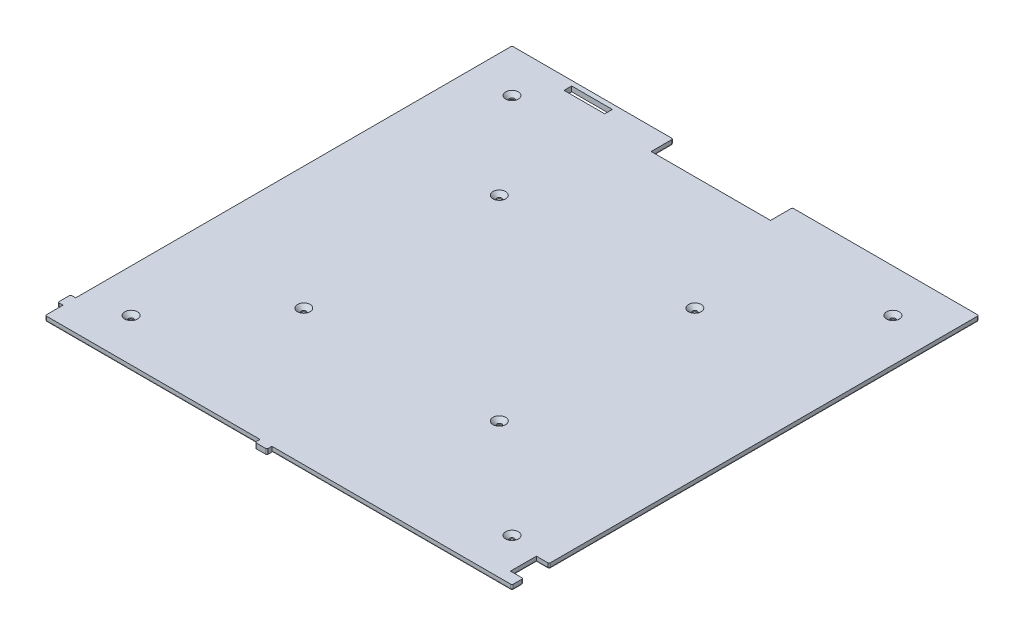
SolidWorks part; units mm, degrees
ref_plane "Front Plane" through (0, 0, 0) normal (0, 0, 1) x (1, 0, 0)
ref_plane "Top Plane" through (0, 0, 0) normal (0, 1, 0) x (1, 0, 0)
ref_plane "Right Plane" through (0, 0, 0) normal (1, 0, 0) x (0, 0, -1)
sketch "Sketch1" plane through (0, 0, 0) normal (0, 1, 0) x (1, 0, 0)
  line L0 (-92, 85.9) -> (-92, -85.9) construction
  line L1 (-28.4, 85.9) -> (-92, 85.9) construction
  line L2 (-28.4, 77.3) -> (-28.4, 85.9) construction
  line L3 (18.4, 77.3) -> (-28.4, 77.3) construction
  line L4 (18.4, 85.9) -> (18.4, 77.3) construction
  line L5 (92, 85.9) -> (18.4, 85.9) construction
  line L6 (92, -83.5) -> (92, 85.9) construction
  line L7 (87, -83.5) -> (92, -83.5) construction
  line L8 (87, -93.5) -> (87, -83.5) construction
  line L9 (92, -93.5) -> (87, -93.5) construction
  line L10 (92, -98.1) -> (92, -93.5) construction
  line L11 (-92, -98.1) -> (92, -98.1) construction
  line L12 (-92, -91.1) -> (-92, -98.1) construction
  line L13 (-94, -91.1) -> (-92, -91.1) construction
  line L14 (-94, -85.9) -> (-94, -91.1) construction
  line L15 (-92, -85.9) -> (-94, -85.9) construction
  line L16 (-91.9, 85.8) -> (-91.9, -86)
  line L17 (-91.9, -86) -> (-93.9, -86)
  line L18 (-93.9, -86) -> (-93.9, -91)
  line L19 (-93.9, -91) -> (-91.9, -91)
  line L20 (-91.9, -91) -> (-91.9, -98)
  line L21 (-91.9, -98) -> (91.9, -98)
  line L22 (91.9, -98) -> (91.9, -93.6)
  line L23 (91.9, -93.6) -> (86.9, -93.6)
  line L24 (86.9, -93.6) -> (86.9, -83.4)
  line L25 (86.9, -83.4) -> (91.9, -83.4)
  line L26 (91.9, -83.4) -> (91.9, 85.8)
  line L27 (91.9, 85.8) -> (18.5, 85.8)
  line L28 (18.5, 85.8) -> (18.5, 77.2)
  line L29 (18.5, 77.2) -> (-28.5, 77.2)
  line L30 (-28.5, 77.2) -> (-28.5, 85.8)
  line L31 (-28.5, 85.8) -> (-91.9, 85.8)
  point P16 (0, -98.1)
  point P18 (-92, 0)
  dimension "D1" = 169.4
  dimension "D2" = 171.8
  dimension "D3" = 63.6
  dimension "D4" = 73.6
  dimension "D5" = 46.8
  dimension "D6" = 8.6
  dimension "D7" = 10
  dimension "D8" = 5
  dimension "D9" = 5.2
  dimension "D10" = 7
  dimension "D11" = 2
  dimension "D12" = 0.1
extrude "Boss-Extrude1" add sketch "Sketch1" along normal blind 2
sketch "Sketch2" plane through (0, 0, 0) normal (0, -1, 0) x (1, 0, 0)
  circle A0 centre (75, -68.9) radius 1
  circle A1 centre (-75, -68.9) radius 1
  circle A2 centre (-75, 81.1) radius 1
  circle A3 centre (75, 81.1) radius 1
  circle A4 centre (33.5, -32.4) radius 1
  circle A5 centre (-43.5, -32.4) radius 1
  circle A6 centre (-43.5, 44.6) radius 1
  circle A7 centre (33.5, 44.6) radius 1
  dimension "D1" = 2
  dimension "D2" = 2
  dimension "D3" = 2
  dimension "D4" = 2
  dimension "D5" = 2
  dimension "D6" = 2
  dimension "D7" = 2
  dimension "D8" = 2
extrude "Cut-Extrude1" cut sketch "Sketch2" against normal through all
chamfer "Chamfer1" distance 1.5 distance2 1.5 1 edges at (-75, 2, -69.9)
chamfer "Chamfer2" distance 1.5 angle 45 7 edges at (75, 2, 80.1) (33.5, 2, 43.6) (75, 2, -69.9) (33.5, 2, -33.4) (-43.5, 2, -33.4) (-43.5, 2, 43.6) (-75, 2, 80.1)
fillet "Fillet1" radius 0.5 16 edges at (-91.9, 0, 0.1) (-92.9, 0, 86) (-93.9, 0, 88.5) (-92.9, 0, 91) (-91.9, 0, 94.5) (0, 0, 98) (91.9, 0, 95.8) (89.4, 0, 93.6) (86.9, 0, 88.5) (89.4, 0, 83.4) (91.9, 0, -1.2) (55.2, 0, -85.8) (18.5, 0, -81.5) (-5, 0, -77.2) (-28.5, 0, -81.5) (-60.2, 0, -85.8)
fillet "Fillet2" radius 0.5 20 edges at (-91.7536, 0.1464, -85.6536) (-28.6464, 0.1464, -85.6536) (18.6464, 0.1464, -85.6536) (91.7536, 0.1464, -85.6536) (91.7536, 0.1464, 83.2536) (91.7536, 0.1464, 93.7464) (91.7536, 0.1464, 97.8536) (-93.7536, 0.1464, 86.1464) (-93.7536, 0.1464, 90.8536) (-91.7536, 0.1464, 97.8536) (-91.9, 1.25, -85.8) (-28.5, 1.25, -85.8) (18.5, 1.25, -85.8) (91.9, 1.25, -85.8) (91.9, 1.25, 83.4) (91.9, 1.25, 93.6) (91.9, 1.25, 98) (-93.9, 1.25, 86) (-93.9, 1.25, 91) (-91.9, 1.25, 98)
sketch "Sketch3" plane through (0, 0, 0) normal (0, -1, 0) x (1, 0, 0)
  line L1 (-50.5, -83.9) -> (-66.5, -83.9)
  line L2 (-50.5, -83.9) -> (-50.5, -80.9)
  line L3 (-50.5, -80.9) -> (-66.5, -80.9)
  line L4 (-66.5, -83.9) -> (-66.5, -80.9)
extrude "Cut-Extrude2" cut sketch "Sketch3" against normal through all
sketch "Sketch4" plane through (0, 2, 0) normal (0, 1, 0) x (1, 0, 0)
  line L0 (-91.4, -98) -> (91.4, -98) construction
  line L1 (-2.65, -98) -> (-7.35, -98)
  line L2 (-2.65, -98) -> (-2.65, -99.95)
  line L3 (-2.65, -99.95) -> (-7.35, -99.95)
  line L4 (-7.35, -98) -> (-7.35, -99.95)
  line L5 (-2.5, -100.1) -> (-2.5, -98.1) construction
  line L6 (-7.5, -100.1) -> (-2.5, -100.1) construction
  line L7 (-7.5, -98.1) -> (-7.5, -100.1) construction
  dimension "D1" = 0.15
  dimension "D2" = 0.15
  dimension "D3" = 0.15
extrude "Boss-Extrude2" add sketch "Sketch4" against normal up to surface (2 mm away) up to face at (-58.5, 0, -82.4)
fillet "Fillet3" radius 0.5 2 edges at (-7.35, 1, 99.95) (-2.65, 1, 99.95)
